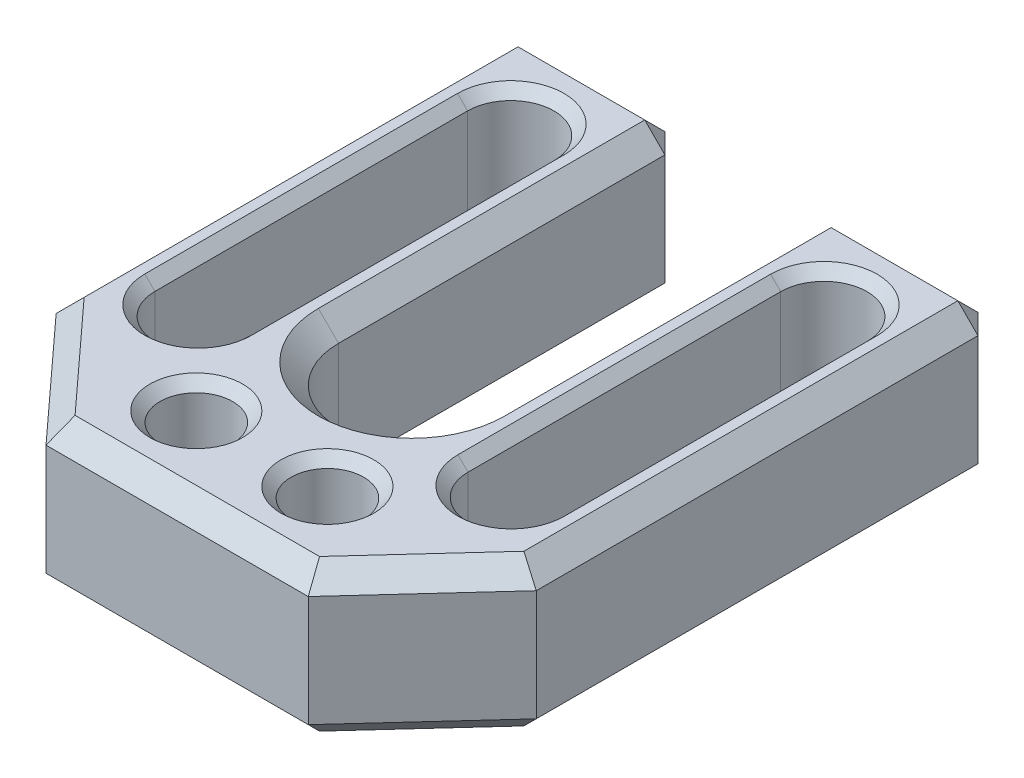
SolidWorks part; units mm, degrees
ref_plane "Front Plane" through (0, 0, 0) normal (0, 0, 1) x (1, 0, 0)
ref_plane "Top Plane" through (0, 0, 0) normal (0, 1, 0) x (1, 0, 0)
ref_plane "Right Plane" through (0, 0, 0) normal (1, 0, 0) x (0, 0, -1)
sketch "Sketch1" plane through (0, 0, 0) normal (0, 1, 0) x (1, 0, 0)
  line L0 (0, 0) -> (0, -3.62) construction
  line L1 (-3.62, 0) -> (-3.62, 17.18)
  line L2 (-3.62, 17.18) -> (-11.9, 17.18)
  line L3 (-11.9, 17.18) -> (-11.9, -5.7175)
  line L4 (-11.9, -5.7175) -> (-6.5, -11.62)
  line L5 (-6.5, -11.62) -> (0, -11.62)
  line L6 (0, -11.62) -> (0, -3.62)
  line L7 (-7.76, 12.68) -> (-7.76, -2.82) construction
  line L8 (-5.62, 12.68) -> (-5.62, -2.82)
  line L9 (-9.9, 12.68) -> (-9.9, -2.82)
  arc A0 (0, -3.62) -> (-3.62, 0) centre (0, 0) cw
  arc A1 (-5.62, 12.68) -> (-9.9, 12.68) centre (-7.76, 12.68) ccw
  arc A2 (-9.9, -2.82) -> (-5.62, -2.82) centre (-7.76, -2.82) ccw
  circle A3 centre (-3.25, -7.42) radius 1.8
  point P12 (-7.76, 4.93)
  dimension "D10" = 3.6
  dimension "D1" = 7.24
  dimension "D2" = 8
  dimension "D3" = 28.8
  dimension "D4" = 8
  dimension "D5" = 23.8
  dimension "D6" = 2
  dimension "D7" = 2
  dimension "D8" = 15.5
  dimension "D9" = 13
  dimension "D11" = 6.5
  dimension "D12" = 4.2
  dimension "D13" = 8.8
extrude "Boss-Extrude1" add sketch "Sketch1" along normal blind 2.5 contours A3 | L6 A0 L1 L2 L3 L4 L5 A3 A2 L9 A1 L8 region at (-2.7801, 0, 2.7801) region at (-3.25, 0, 7.42)
extrude "Boss-Extrude2" add sketch "Sketch1<4>" along normal blind 5 from surface starting at face at (-7.76, 2.5, -4.93)
sketch "Sketch1<4>" plane through (0, 0, 0) normal (0, 1, 0) x (1, 0, 0) same geometry as "Sketch1"
chamfer "Chamfer1" distance 1 angle 45 14 edges at (-2.5597, 0, 2.5597) (-2.5597, 7.5, 2.5597) (-11.9, 3.75, -17.18) (-3.62, 0, -8.59) (-3.25, 0, 11.62) (-9.2, 0, 8.6687) (-11.9, 0, -5.7313) (-7.76, 0, -17.18) (-3.62, 3.75, -17.18) (-3.25, 7.5, 11.62) (-9.2, 7.5, 8.6687) (-11.9, 7.5, -5.7313) (-7.76, 7.5, -17.18) (-3.62, 7.5, -8.59)
chamfer "Chamfer2" distance 0.5 angle 45 9 edges at (-7.76, 0, -14.82) (-9.9, 0, -4.93) (-5.62, 0, -4.93) (-7.76, 0, 4.96) (-7.76, 7.5, -14.82) (-9.9, 7.5, -4.93) (-5.62, 7.5, -4.93) (-7.76, 7.5, 4.96) (-3.25, 7.5, 9.22)
mirror "Mirror1" about plane through (0, 2.5, 0) normal (-1, 0, 0) of bodies 102
equation "\"D7@Sketch1\"=\"D6@Sketch1\""
